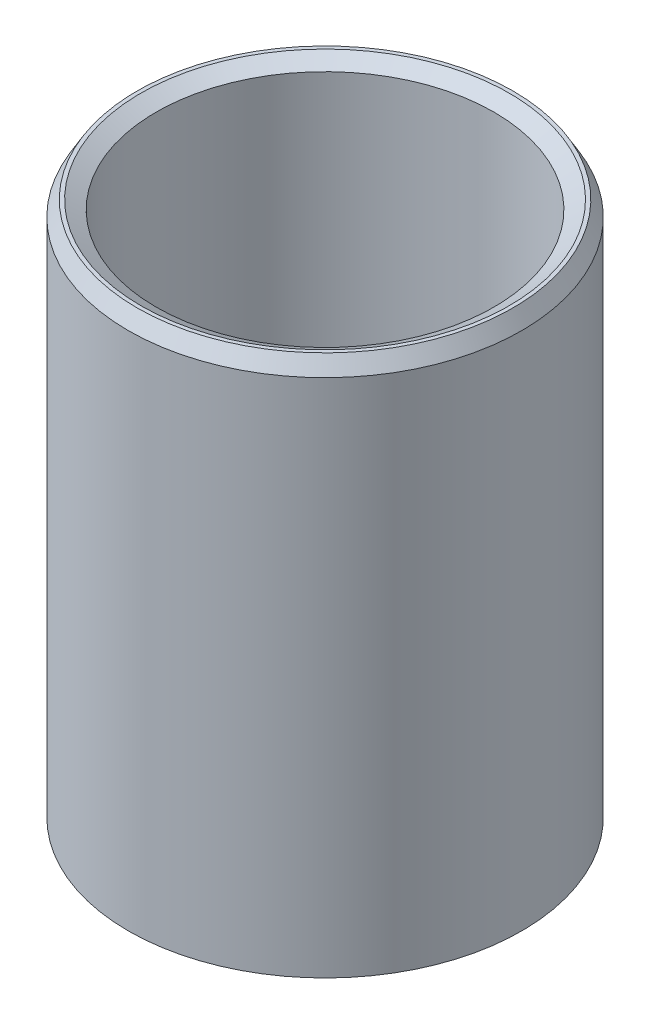
SolidWorks part; units mm, degrees
ref_plane "Front Plane" through (0, 0, 0) normal (0, 0, 1) x (1, 0, 0)
ref_plane "Top Plane" through (0, 0, 0) normal (0, 1, 0) x (1, 0, 0)
ref_plane "Right Plane" through (0, 0, 0) normal (1, 0, 0) x (0, 0, -1)
sketch "Sketch1" plane through (0, 0, 0) normal (0, 1, 0) x (1, 0, 0)
  circle A0 centre (0, 0) radius 47.5
  dimension "SLEEVE_OD" = 95
extrude "Boss-Extrude1" add sketch "Sketch1" along normal blind 131.323
sketch "Sketch2" plane through (0, 0, 0) normal (0, 1, 0) x (1, 0, 0)
  circle A0 centre (0, 0) radius 40.7822
  dimension "BORE_D" = 81.5645
extrude "Cut-Extrude1" cut sketch "Sketch2" along normal through all
chamfer "Chamfer1" distance 3.6829 angle 30 4 edges at (0, 131.323, 40.7822) (0, 0, 40.7822) (0, 0, 47.5) (0, 131.323, 47.5) first distance on face at (0, 131.323, 40.7822) first distance on face at (0, 0, 40.7822) first distance on face at (0, 131.323, 47.5)
